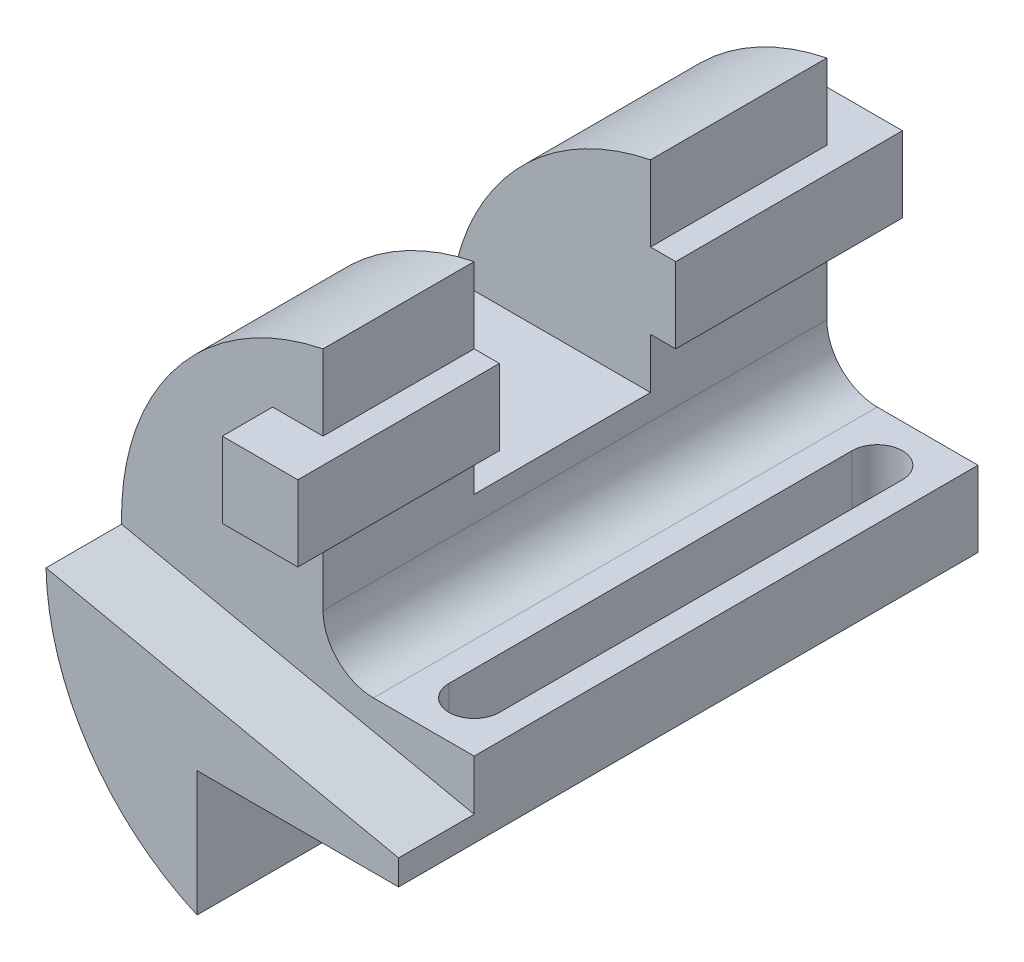
SolidWorks part; units mm, degrees
note: The reader was unsure of these and kept them because the rebuilt part matched: shared geometry of "Sketch1<5>".
material "1060 Alloy"
ref_plane "Front Plane" through (0, 0, 0) normal (0, 0, 1) x (1, 0, 0)
ref_plane "Top Plane" through (0, 0, 0) normal (0, 1, 0) x (1, 0, 0)
ref_plane "Right Plane" through (0, 0, 0) normal (1, 0, 0) x (0, 0, -1)
other "Center of Mass"
sketch "Sketch1" plane through (0, 0, 0) normal (0, 0, 1) x (1, 0, 0)
  line L5 (-178.4995, 0) -> (178.4995, 0) construction
  line L6 (0, -185.1274) -> (0, 185.1274) construction
  line L7 (-10, 94.8156) -> (-10, 49.8156)
  line L8 (0, 39.8156) -> (20, 39.8156)
  line L9 (20, 39.8156) -> (20, 24.8156)
  line L10 (20, 24.8156) -> (-20, 24.8156)
  line L11 (-20, 24.8156) -> (-20, 0)
  line L12 (-49.9871, 44.6918) -> (20, 29.8156)
  line L13 (-5, 79.8156) -> (-20, 79.8156)
  line L14 (-5, 79.8156) -> (-5, 64.8156)
  line L15 (-5, 64.8156) -> (-20, 64.8156)
  line L16 (-20, 79.8156) -> (-20, 64.8156)
  arc A2 (-20, 0) -> (-10, 94.8156) centre (0, 45.8258) cw
  arc A3 (-10, 49.8156) -> (0, 39.8156) centre (0, 49.8156) ccw
  point P3 (0, 0)
  point P6 (0, 0)
  point P21 (-48.4413, 33.4385)
  point P22 (20, 16.1511)
  point P23 (-18.9487, 82.0658)
  point P24 (-18.9818, 84.4289)
  point P25 (-20, 66.1845)
  point P27 (-5, 81.0139)
  dimension "D1" = 10
  dimension "D5" = 10
  dimension "D2" = 50
  dimension "D3" = 20
  dimension "D4" = 40
  dimension "D6" = 5
  dimension "D7" = 15
  dimension "D8" = 78
  dimension "D9" = 5
  dimension "D10" = 15
  dimension "D11" = 55
  dimension "D12" = 15
  dimension "D13" = 15
extrude "Boss-Extrude1" add sketch "Sketch1" against normal blind 115 contours A3 L7 L15 L16 L13 A2 L12 L9 L8 | A2 L11 L10 L9 L12 | L13 L16 L15 L7
sketch "Sketch5" plane through (-10, 0, 0) normal (1, 0, 0) x (0, 0, -1)
  line L0 (115, 94.8156) -> (0, 94.8156) construction
  line L1 (30, 94.8156) -> (54.925, 94.8156)
  line L2 (30, 94.8156) -> (30, 59.7345)
  line L3 (30, 59.7345) -> (54.925, 59.7345)
  line L4 (54.925, 94.8156) -> (54.925, 59.7345)
  line L5 (0, 94.8156) -> (0, 49.8156) construction
  dimension "D1" = 30
extrude "Cut-Extrude1" cut sketch "Sketch1<5>" against normal blind 15 contours A3 L7 L15 L16 L13 A2 L12 L9 L8 | L13 L16 L15 L7
sketch "Sketch1<5>" plane through (0, 0, 0) normal (0, 0, 1) x (1, 0, 0) same geometry as "Sketch1"
ref_plane "Plane1" through (0, 0, -57.5) normal (0, 0, 1) x (1, 0, 0)
sketch "Sketch6" plane through (0, 0, -57.5) normal (0, 0, 1) x (1, 0, 0)
  line L0 (-5, 79.8156) -> (-20, 79.8156) construction
  line L1 (-5, 79.8156) -> (-5, 64.8156) construction
  line L2 (-20, 79.8156) -> (-20, 64.8156) construction
  line L3 (-5, 64.8156) -> (-20, 64.8156) construction
  line L4 (-5, 79.8156) -> (-20, 79.8156)
  line L5 (-5, 79.8156) -> (-5, 64.8156)
  line L6 (-20, 79.8156) -> (-20, 64.8156)
  line L7 (-5, 64.8156) -> (-20, 64.8156)
extrude "Boss-Extrude3" add sketch "Sketch6" along normal offset from surface 10 and the other way offset from surface (67.5 mm away) 10 up to face at (-6.8584, 50.6587, -15) offset beyond the face yes other way up to face at (-8.1136, 39.3549, -115)
sketch "Sketch7" plane through (-5, 0, 0) normal (1, 0, 0) x (0, 0, -1)
  line L0 (115, 94.8156) -> (15, 94.8156) construction
  line L1 (45, 94.8156) -> (80, 94.8156)
  line L2 (45, 94.8156) -> (45, 54.8156)
  line L3 (45, 54.8156) -> (80, 54.8156)
  line L4 (80, 94.8156) -> (80, 54.8156)
  line L5 (15, 64.8156) -> (15, 49.8156) construction
  line L6 (5, 64.8156) -> (125, 64.8156) construction
  dimension "D1" = 30
  dimension "D2" = 35
  dimension "D3" = 10
extrude "Cut-Extrude2" cut sketch "Sketch7" against normal up to surface (5 mm away)
sketch "Sketch8" plane through (0, 39.8156, 0) normal (0, 1, 0) x (1, 0, 0)
  line L0 (10, 25) -> (10, 105) construction
  line L1 (5, 25) -> (5, 105)
  line L2 (15, 25) -> (15, 105)
  line L3 (20, 115) -> (20, 15) construction
  line L5 (-49.9871, 15) -> (20, 15) construction
  arc A0 (5, 25) -> (15, 25) centre (10, 25) ccw
  arc A1 (15, 105) -> (5, 105) centre (10, 105) ccw
  point P2 (10, 65)
  dimension "D1" = 80
  dimension "D2" = 10
  dimension "D3" = 10
  dimension "D4" = 10
extrude "Cut-Extrude3" cut sketch "Sketch8" against normal up to surface (15 mm away) up to face at (0, 24.8156, -57.5)
